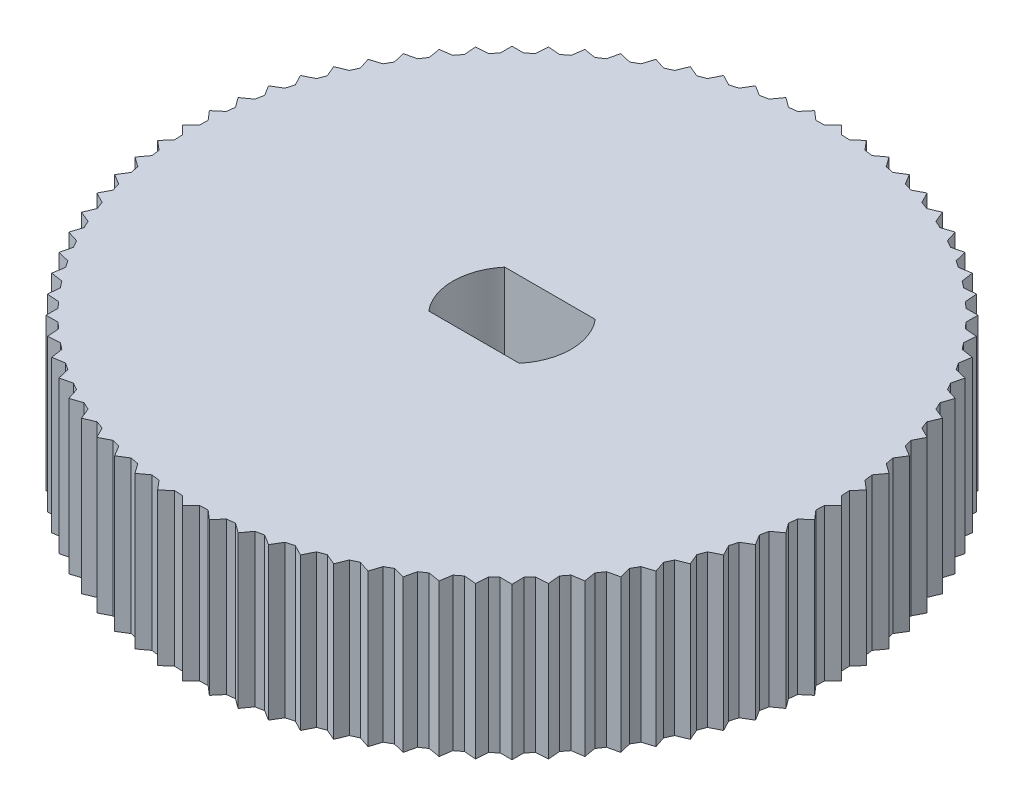
SolidWorks part; units mm, degrees
ref_plane "Front Plane" through (0, 0, 0) normal (0, 0, 1) x (1, 0, 0)
ref_plane "Top Plane" through (0, 0, 0) normal (0, 1, 0) x (1, 0, 0)
ref_plane "Right Plane" through (0, 0, 0) normal (1, 0, 0) x (0, 0, -1)
sketch "Sketch1" plane through (0, 0, 0) normal (0, 1, 0) x (1, 0, 0)
  line L1 (-2.6795, 2.25) -> (2.6795, 2.25)
  line L3 (-2.6795, -2.25) -> (2.6795, -2.25)
  arc A0 (-2.6795, 2.25) -> (-2.6795, -2.25) centre (0, 0) ccw
  arc A1 (2.6795, -2.25) -> (2.6795, 2.25) centre (0, 0) ccw
  circle A2 centre (0, 0) radius 19
  dimension "D1" = 4.5
  dimension "D2" = 38
  dimension "D4" = 3.4989
  dimension "D3" = 5.359
extrude "Boss-Extrude1" add sketch "Sketch1" along normal blind 9
ref_axis "Axis1" through (0, 9, 0) along (0, -1, 0)
sketch "Sketch4" plane through (0, 9, 0) normal (0, 1, 0) x (1, 0, 0)
  line L0 (-0.5, 18.9934) -> (0, 19.5)
  line L1 (0, 19.5) -> (0.5, 18.9934)
  line L2 (-0.5, 18.9934) -> (0.5, 18.9934)
  circle A0 centre (0, 0) radius 19 construction
  point P4 (0.4208, 18.9953)
  dimension "D1" = 19.5
  dimension "D2" = 1
extrude "Boss-Extrude2" add sketch "Sketch4" against normal up to surface (9 mm away) up to face at (0, 0, 19)
pattern_circular "CirPattern1" count 80 over 360 about axis through (0, 9, 0) along (0, -1, 0) of "Boss-Extrude2"
